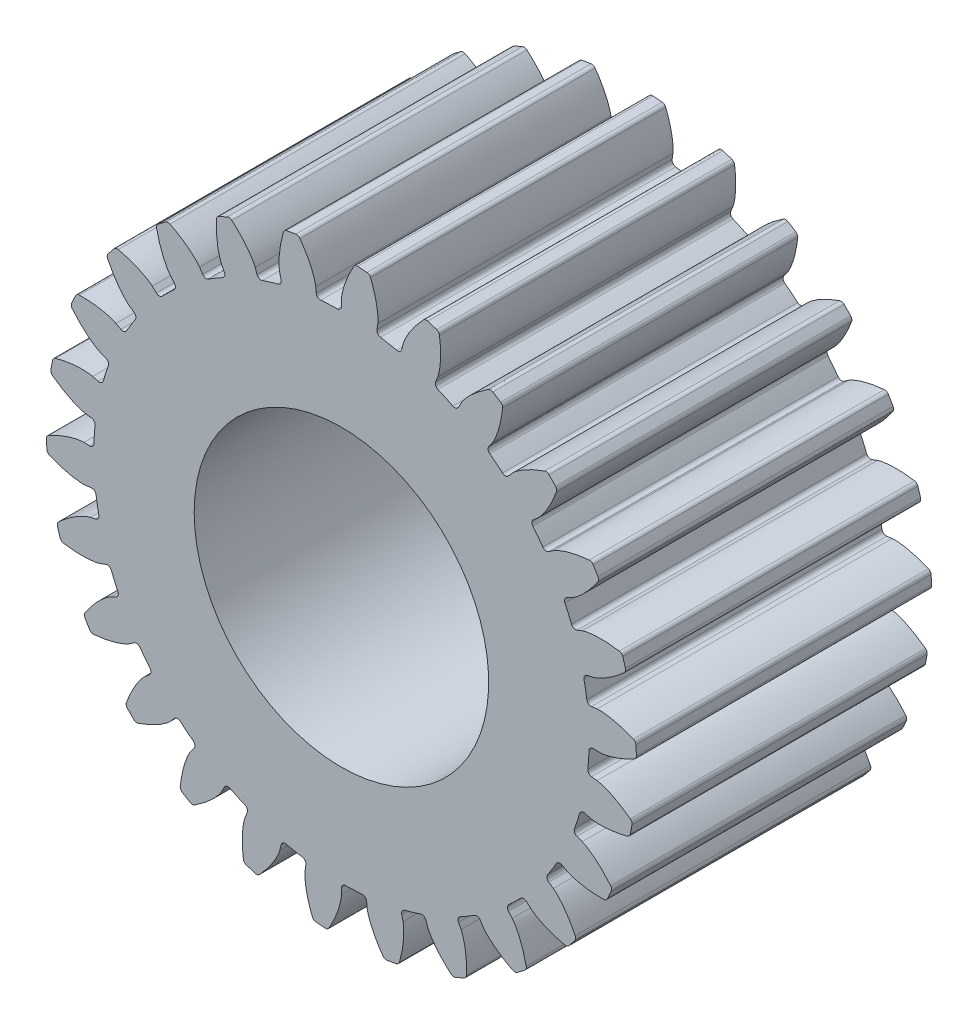
SolidWorks part; units mm, degrees
ref_plane "Front Plane" through (0, 0, 0) normal (0, 0, 1) x (1, 0, 0)
ref_plane "Top Plane" through (0, 0, 0) normal (0, 1, 0) x (1, 0, 0)
ref_plane "Right Plane" through (0, 0, 0) normal (1, 0, 0) x (0, 0, -1)
sketch "Involute Geometry" plane through (0, 0, 0) normal (0, 0, 1) x (1, 0, 0)
  line L0 (0, 12.216) -> (0, 0) construction
  line L1 (0, 0) -> (0.9904, 13.9649) construction
  line L2 (1.724, 12.0937) -> (0, 0) construction
  line L3 (0.175, 12.9988) -> (0, 0) construction
  line L4 (0, 0) -> (1.6612, 12.8934) construction
  circle A1 centre (0, 0) radius 12.216 construction
  circle A2 centre (0, 0) radius 13 construction
  circle A3 centre (0, 0) radius 14 construction
  circle A4 centre (0, 0) radius 11.75 construction
  arc A5 (0.6454, 13.9851) -> (1.3347, 13.9362) centre (0, 0) cw
  arc A6 (0.175, 12.9988) -> (1.6612, 12.8934) centre (0, 0) cw construction
  spline S0 degree 4 poles (0, 12.216) (0, 12.2259) (0.0007, 12.2537) (0.0046, 12.3061) (0.0149, 12.3914) (0.0336, 12.4994) (0.064, 12.638) (0.108, 12.7997) (0.1647, 12.9755) (0.2354, 13.1642) (0.3138, 13.35) (0.3992, 13.5328) (0.4907, 13.7124) (0.6089, 13.9268) (0.7611, 14.1794) (0.9535, 14.4672) (1.1888, 14.7846) (1.4461, 15.0973) (1.7136, 15.3959) (1.9994, 15.6864) (2.287, 15.9594) (2.6008, 16.2305) (2.8982, 16.4744) (3.2472, 16.733) (3.5335, 16.9374) (3.9271, 17.1908) (4.1642, 17.3355) (4.4469, 17.4991) (4.5752, 17.5686) (4.654, 17.6115) knots 0 0 0 0 0 0.005377 0.015084 0.028532 0.04661 0.064855 0.092111 0.119476 0.146842 0.174209 0.201575 0.228941 0.256307 0.307035 0.361767 0.4165 0.471232 0.525964 0.580697 0.635429 0.690161 0.744894 0.799626 0.854358 0.909091 0.954545 1 1 1 1 1 construction
  spline S1 degree 4 poles (0, 12.216) (0, 12.2259) (0.0007, 12.2537) (0.0046, 12.3061) (0.0149, 12.3914) (0.0336, 12.4994) (0.064, 12.638) (0.108, 12.7997) (0.1647, 12.9755) (0.2354, 13.1642) (0.3138, 13.35) (0.3992, 13.5328) (0.4907, 13.7124) (0.6089, 13.9268) (0.7611, 14.1794) (0.9535, 14.4672) (1.1888, 14.7846) (1.4461, 15.0973) (1.7136, 15.3959) (1.9994, 15.6864) (2.287, 15.9594) (2.6008, 16.2305) (2.8982, 16.4744) (3.2472, 16.733) (3.5335, 16.9374) (3.8418, 17.1359) (3.9936, 17.2306) (4.0719, 17.2782) knots 0 0 0 0 0 0.005377 0.015084 0.028532 0.04661 0.064855 0.092111 0.119476 0.146842 0.174209 0.201575 0.228941 0.256307 0.307035 0.361767 0.4165 0.471232 0.525964 0.580697 0.635429 0.690161 0.744894 0.799626 0.854358 0.909091 0.909091 0.909091 0.909091 0.909091
  spline S3 degree 4 poles (1.724, 12.0937) (1.7254, 12.1035) (1.7287, 12.1311) (1.7321, 12.1836) (1.734, 12.2695) (1.7308, 12.379) (1.7202, 12.5206) (1.6995, 12.6869) (1.6681, 12.8689) (1.6248, 13.0657) (1.5734, 13.2607) (1.5147, 13.4537) (1.4495, 13.6444) (1.3626, 13.8734) (1.2477, 14.1449) (1.0977, 14.457) (0.9096, 14.8044) (0.699, 15.1503) (0.4764, 15.4836) (0.2344, 15.8116) (-0.0118, 16.1224) (-0.2842, 16.4351) (-0.5442, 16.7185) (-0.8532, 17.0238) (-1.1078, 17.2666) (-1.4617, 17.573) (-1.676, 17.7497) (-1.9328, 17.9515) (-2.05, 18.0384) (-2.122, 18.092) knots 0 0 0 0 0 0.005377 0.015084 0.028532 0.04661 0.064855 0.092111 0.119476 0.146842 0.174209 0.201575 0.228941 0.256307 0.307035 0.361767 0.4165 0.471232 0.525964 0.580697 0.635429 0.690161 0.744894 0.799626 0.854358 0.909091 0.954545 1 1 1 1 1 construction
  spline S4 degree 4 poles (1.724, 12.0937) (1.7254, 12.1035) (1.7287, 12.1311) (1.7321, 12.1836) (1.734, 12.2695) (1.7308, 12.379) (1.7202, 12.5206) (1.6995, 12.6869) (1.6681, 12.8689) (1.6248, 13.0657) (1.5734, 13.2607) (1.5147, 13.4537) (1.4495, 13.6444) (1.3626, 13.8734) (1.2477, 14.1449) (1.0977, 14.457) (0.9096, 14.8044) (0.699, 15.1503) (0.4764, 15.4836) (0.2344, 15.8116) (-0.0118, 16.1224) (-0.2842, 16.4351) (-0.5442, 16.7185) (-0.8532, 17.0238) (-1.1078, 17.2666) (-1.385, 17.5066) (-1.5219, 17.6217) (-1.5927, 17.6799) knots 0 0 0 0 0 0.005377 0.015084 0.028532 0.04661 0.064855 0.092111 0.119476 0.146842 0.174209 0.201575 0.228941 0.256307 0.307035 0.361767 0.4165 0.471232 0.525964 0.580697 0.635429 0.690161 0.744894 0.799626 0.854358 0.909091 0.909091 0.909091 0.909091 0.909091
  dimension "D5" = 6.57
sketch "Sketch2" plane through (0, 0, 0) normal (0, 0, 1) x (1, 0, 0)
  circle A0 centre (0, 0) radius 11.75 construction
  circle A1 centre (0, 0) radius 11.75
extrude "Boss-Extrude1" add sketch "Sketch2" along normal mid plane 14
sketch "Sketch3" plane through (0, 0, 0) normal (0, 0, 1) x (1, 0, 0)
  line L0 (0, 12.216) -> (0, 0) construction
  line L1 (1.724, 12.0937) -> (0, 0) construction
  line L2 (0, 12.216) -> (0, 11.75)
  line L4 (1.724, 12.0937) -> (1.6583, 11.6324)
  circle A1 centre (0, 0) radius 11.75 construction
  arc A3 (0, 11.75) -> (1.6583, 11.6324) centre (0, 0) cw
  arc A4 (1.3347, 13.9362) -> (0.6454, 13.9851) centre (0, 0) ccw construction
  arc A5 (1.3347, 13.9362) -> (0.6454, 13.9851) centre (0, 0) ccw
  spline S0 degree 4 poles (999.8581, 25.2356) (18.0155, 10.2173) (0.3577, 10.7107) (-0.0848, 11.5636) (0.0149, 12.3914) (0.0336, 12.4994) (0.064, 12.638) (0.108, 12.7997) (0.1647, 12.9755) (0.2354, 13.1642) (0.3138, 13.35) (0.3992, 13.5328) (0.4907, 13.7124) (0.6089, 13.9268) (0.7611, 14.1794) (0.9535, 14.4672) (1.1888, 14.7846) (1.4461, 15.0973) (1.7136, 15.3959) (1.9994, 15.6864) (2.287, 15.9594) (2.6008, 16.2305) (2.8982, 16.4744) (3.2472, 16.733) (4.4419, 17.5861) (8.1221, 19.6216) (-23.9178, -0.2396) (859.2438, 535.5339) knots -0.405932 -0.405932 -0.405932 -0.405932 -0.405932 0.005377 0.015084 0.028532 0.04661 0.064855 0.092111 0.119476 0.146842 0.174209 0.201575 0.228941 0.256307 0.307035 0.361767 0.4165 0.471232 0.525964 0.580697 0.635429 0.690161 0.744894 0.799626 0.854358 1.603617 1.603617 1.603617 1.603617 1.603617 only from (0, 12.216) to (3.8711, 11.595) construction
  spline S1 degree 4 poles (0, 12.216) (0, 12.2259) (0.0007, 12.2537) (0.0046, 12.3061) (0.0149, 12.3914) (0.0336, 12.4994) (0.064, 12.638) (0.108, 12.7997) (0.1647, 12.9755) (0.2354, 13.1642) (0.3138, 13.35) (0.3992, 13.5328) (0.4919, 13.7149) (0.5664, 13.8498) (0.6183, 13.9394) (0.6454, 13.9851) knots 0 0 0 0 0 0.005377 0.015084 0.028532 0.04661 0.064855 0.092111 0.119476 0.146842 0.174209 0.201575 0.228941 0.257808 0.257808 0.257808 0.257808 0.257808
  spline S3 degree 4 poles (-986.2895, 166.0908) (-16.3932, 12.6575) (1.1575, 10.654) (1.7159, 11.4359) (1.734, 12.2695) (1.7308, 12.379) (1.7202, 12.5206) (1.6995, 12.6869) (1.6681, 12.8689) (1.6248, 13.0657) (1.5734, 13.2607) (1.5147, 13.4537) (1.4495, 13.6444) (1.3626, 13.8734) (1.2477, 14.1449) (1.0977, 14.457) (0.9096, 14.8044) (0.699, 15.1503) (0.4764, 15.4836) (0.2344, 15.8116) (-0.0118, 16.1224) (-0.2842, 16.4351) (-0.5442, 16.7185) (-0.8532, 17.0238) (-1.9155, 18.037) (-5.2716, 20.5715) (23.6446, -3.6127) (-775.0652, 651.4371) knots -0.405932 -0.405932 -0.405932 -0.405932 -0.405932 0.005377 0.015084 0.028532 0.04661 0.064855 0.092111 0.119476 0.146842 0.174209 0.201575 0.228941 0.256307 0.307035 0.361767 0.4165 0.471232 0.525964 0.580697 0.635429 0.690161 0.744894 0.799626 0.854358 1.603617 1.603617 1.603617 1.603617 1.603617 only from (1.724, 12.0937) to (-1.5927, 17.6799) construction
  spline S4 degree 4 poles (1.724, 12.0937) (1.7254, 12.1035) (1.7287, 12.1311) (1.7321, 12.1836) (1.734, 12.2695) (1.7308, 12.379) (1.7202, 12.5206) (1.6995, 12.6869) (1.6681, 12.8689) (1.6248, 13.0657) (1.5734, 13.2607) (1.5147, 13.4537) (1.4486, 13.647) (1.3938, 13.7911) (1.3551, 13.8871) (1.3347, 13.9362) knots 0 0 0 0 0 0.005377 0.015084 0.028532 0.04661 0.064855 0.092111 0.119476 0.146842 0.174209 0.201575 0.228941 0.257808 0.257808 0.257808 0.257808 0.257808
extrude "Boss-Extrude2" add sketch "Sketch3" along normal through all and the other way through all
fillet "Fillet2" [suppressed] radius 0.381
pattern_circular "CirPattern1" count 26 over 360 about axis through (0, 0, 7) along (0, 0, -1) of "Boss-Extrude2", "Fillet2"
ref_axis "Axis1" through (0, 0, 7) along (0, 0, -1)
sketch "Sketch4" plane through (0, 0, -7) normal (0, 0, -1) x (-1, 0, 0)
  circle A1 centre (0, 0) radius 6.985
  dimension "D1" = 13.97
extrude "Cut-Extrude1" cut sketch "Sketch4" against normal through all
fillet "Fillet3" radius 0.2 104 edges at (-8.6313, 7.9727, 0) (-9.6701, 6.6748, 0) (-10.9864, 4.1666, 0) (-11.3477, 3.0483, 0) (-11.6643, 1.4163, 0) (-11.7475, 0.244, 0) (-11.6643, -1.4163, 0) (-11.4645, -2.5744, 0) (-10.9864, -4.1666, 0) (-10.5153, -5.2432, 0) (-9.6701, -6.6748, 0) (-8.9549, -7.6074, 0) (-7.7917, -8.795, 0) (-6.8742, -9.5293, 0) (-5.4605, -10.4041, 0) (-4.3939, -10.8975, 0) (-2.812, -11.4086, 0) (-1.6583, -11.6324, 0) (0, -11.75, 0) (1.1737, -11.6912, 0) (2.812, -11.4086, 0) (3.9375, -11.0706, 0) (5.4605, -10.4041, 0) (6.4725, -9.8066, 0) (7.7917, -8.795, 0) (8.6313, -7.9727, 0) (9.6701, -6.6748, 0) (10.2885, -5.6754, 0) (10.9864, -4.1666, 0) (11.3477, -3.0483, 0) (11.6643, -1.4163, 0) (11.7475, -0.244, 0) (11.6643, 1.4163, 0) (11.4645, 2.5744, 0) (10.9864, 4.1666, 0) (10.5153, 5.2432, 0) (9.6701, 6.6748, 0) (8.9549, 7.6074, 0) (7.7917, 8.795, 0) (6.8742, 9.5293, 0) (5.4605, 10.4041, 0) (4.3939, 10.8975, 0) (2.812, 11.4086, 0) (1.6583, 11.6324, 0) (0, 11.75, 0) (-10.2885, 5.6754, 0) (-1.1737, 11.6912, 0) (-2.812, 11.4086, 0) (-3.9375, 11.0706, 0) (-5.4605, 10.4041, 0) (-6.4725, 9.8066, 0) (-7.7917, 8.795, 0) (1.3347, 13.9362, 0) (3.9735, 13.4243, 0) (4.6311, 13.2119, 0) (7.0707, 12.0833, 0) (7.6583, 11.7197, 0) (9.757, 10.04, 0) (10.2405, 9.5463, 0) (11.8762, 7.4133, 0) (12.2275, 6.8182, 0) (13.3052, 4.3557, 0) (13.5039, 3.6939, 0) (13.9609, 1.045, 0) (13.9955, 0.3548, 0) (13.8053, -2.3265, 0) (13.6737, -3.0048, 0) (12.8474, -5.5627, 0) (12.5573, -6.1898, 0) (11.1429, -8.4756, 0) (10.7111, -9.0151, 0) (8.7907, -10.896, 0) (8.2424, -11.3165, 0) (5.9277, -12.6832, 0) (5.2947, -12.9602, 0) (2.7202, -13.7332, 0) (2.0392, -13.8507, 0) (-0.6454, -13.9851, 0) (-1.3347, -13.9362, 0) (-3.9735, -13.4243, 0) (-4.6311, -13.2119, 0) (-7.0707, -12.0833, 0) (-7.6583, -11.7197, 0) (-9.757, -10.04, 0) (-10.2405, -9.5463, 0) (-11.8762, -7.4133, 0) (-12.2275, -6.8182, 0) (-13.3052, -4.3557, 0) (-13.5039, -3.6939, 0) (-13.9609, -1.045, 0) (-13.9955, -0.3548, 0) (-13.8053, 2.3265, 0) (-13.6737, 3.0048, 0) (-12.8474, 5.5627, 0) (-12.5573, 6.1898, 0) (-11.1429, 8.4756, 0) (-10.7111, 9.0151, 0) (-8.7907, 10.896, 0) (-8.2424, 11.3165, 0) (-5.9277, 12.6832, 0) (-5.2947, 12.9602, 0) (-2.7202, 13.7332, 0) (-2.0392, 13.8507, 0) (0.6454, 13.9851, 0)
equation "\"N\"= 26'Number of Teeth"
equation "\"m\"= 1mm'Diametral Pitch"
equation "\"phi\"= 20deg'Pressure Angle"
equation "\"a\"= \"m\"'Addendum"
equation "\"b\"= 1.25 * \"m\"'Dedendum"
equation "\"Dp\"= \"N\" * \"m\"'Pitch diameter"
equation "\"Db\"= \"Dp\" * cos ( \"phi\" )'Base diameter"
equation "\"D1@Involute Geometry\" = \"Db\""
equation "\"D2@Involute Geometry\" = \"Dp\""
equation "\"D3@Involute Geometry\" = \"Dp\" + 2 * \"a\""
equation "\"D4@Involute Geometry\" = \"Dp\" - 2 * \"b\""
equation "\"D1@CirPattern1\"=\"N\""
equation "\"D5@Involute Geometry\"=180/\"N\"-\"j_th\"/2"
equation "\"D1@Boss-Extrude1\"=14*\"m\""
equation "\"j_th\"= ( 360deg ) * ( 0.16mm ) / ( pi * \"Dp\" )'Angular backlash"
equation "\"alpha\"= sqr ( \"Dp\" ^ 2 - \"Db\" ^ 2 ) / \"Db\" * 180 / pi - \"phi\""
equation "\"beta\"= ( ( 360deg / \"N\" ) / 4 - \"alpha\" )"
